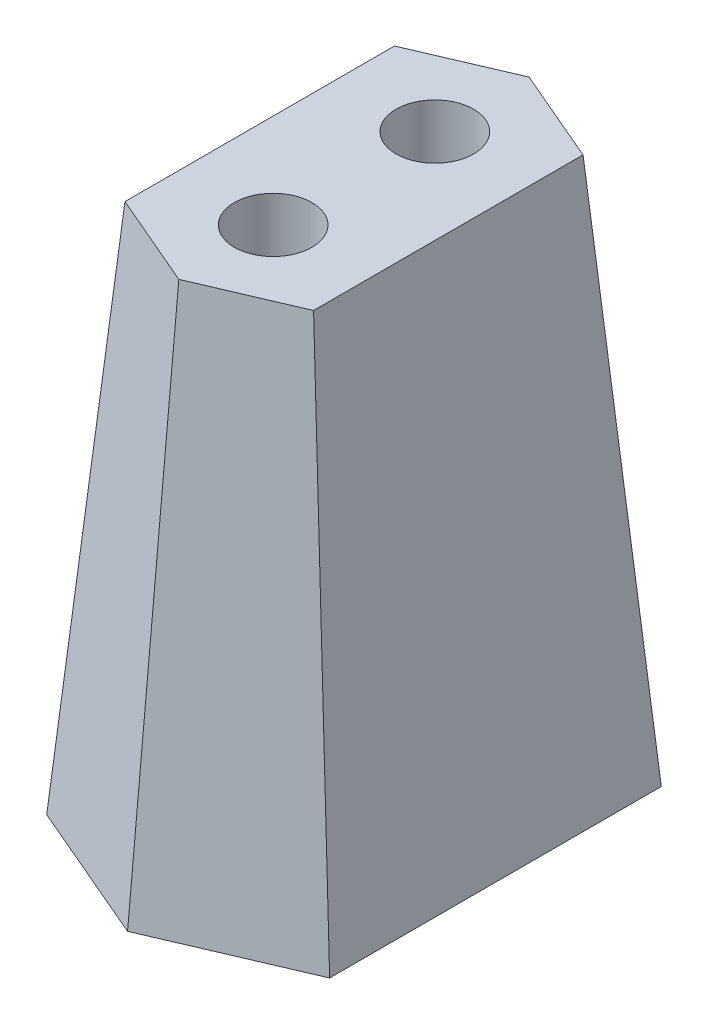
SolidWorks part; units mm, degrees
ref_plane "Front Plane" through (0, 0, 0) normal (0, 0, 1) x (1, 0, 0)
ref_plane "Top Plane" through (0, 0, 0) normal (0, 1, 0) x (1, 0, 0)
ref_plane "Right Plane" through (0, 0, 0) normal (1, 0, 0) x (0, 0, -1)
sketch "Sketch1" plane through (0, 0, 0) normal (0, 1, 0) x (1, 0, 0)
  line L0 (0, -6.5) -> (0, 6.5) construction
  line L1 (-3.5, 0) -> (3.5, 0) construction
  line L2 (3.5, -5) -> (3.5, 5)
  line L3 (-3.5, -5) -> (-3.5, 5)
  line L4 (-3.5, 5) -> (0, 6.5)
  line L5 (0, 6.5) -> (3.5, 5)
  line L6 (3.5, -5) -> (0, -6.5)
  line L7 (0, -6.5) -> (-3.5, -5)
  point P4 (0, 0)
  point P8 (0, 0)
  point P11 (3.5, 0)
  point P14 (-3.5, 0)
  dimension "D1" = 10
  dimension "D2" = 13
  dimension "D3" = 7
extrude "Boss-Extrude1" add sketch "Sketch1" along normal blind 20
sketch "Sketch2" plane through (0, 20, 0) normal (0, 1, 0) x (1, 0, 0)
  line L0 (0, -3) -> (0, 3) construction
  circle A0 centre (0, 3) radius 1.44
  circle A1 centre (0, -3) radius 1.44
  point P4 (0, 0)
  dimension "D1" = 2.88
  dimension "D2" = 6
extrude "Cut-Extrude1" cut sketch "Sketch2" against normal through all
draft "Draft1" type of draft neutral plane draft angle 5 faces to draft 6 face at (-3.5, 10, 0) face at (-1.75, 10, -5.75) face at (1.75, 10, -5.75) face at (3.5, 10, 0) face at (1.75, 10, 5.75) face at (-1.75, 10, 5.75) neutral plane through (0, 20, 0) neutral plane normal (0, 1, 0) parameters "D1"=5
extrude "Cut-Extrude2" cut sketch "Sketch1<2>" along normal blind 5
sketch "Sketch1<2>" plane through (0, 0, 0) normal (0, 1, 0) x (1, 0, 0) same geometry as "Sketch1"
draft "Draft2" type of draft neutral plane draft angle 10 faces to draft 6 face at (-3.5, 2.5, 0) face at (-1.75, 2.5, 5.75) face at (1.75, 2.5, 5.75) face at (3.5, 2.5, 0) face at (1.75, 2.5, -5.75) face at (-1.75, 2.5, -5.75) neutral plane through (0, 5, 0) neutral plane normal (0, -1, 0) parameters "D1"=10
